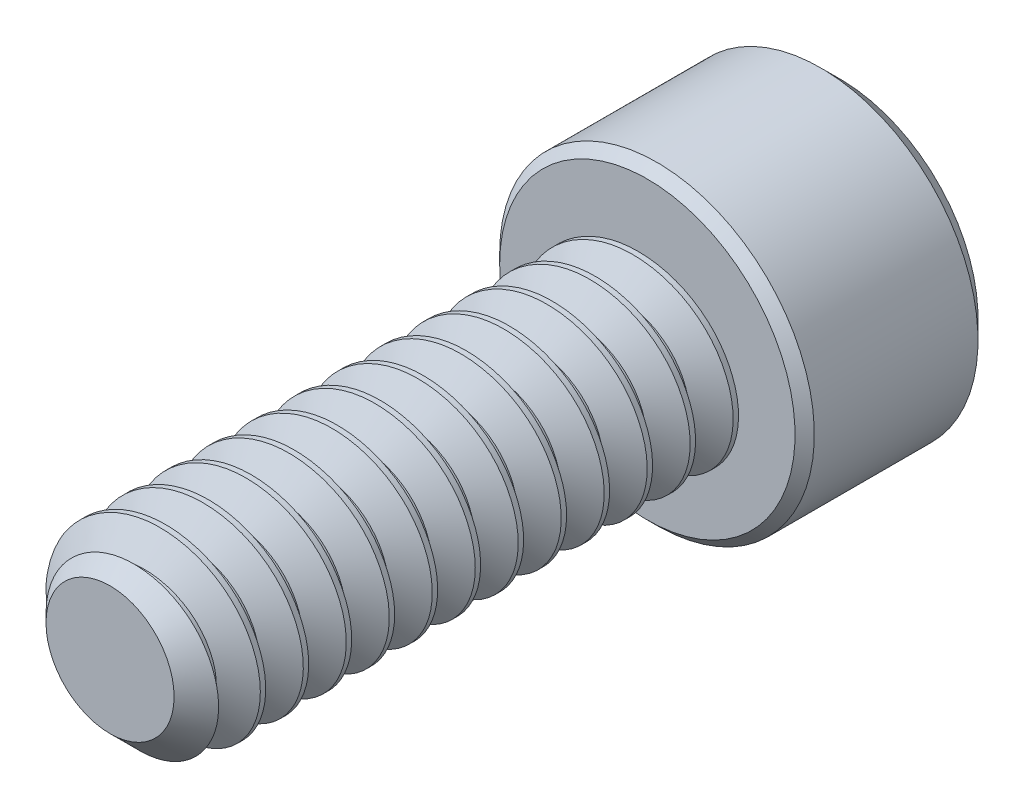
SolidWorks part; units mm, degrees
material "Plain Carbon Steel"
ref_plane "Front Plane" through (0, 0, 0) normal (0, 0, 1) x (1, 0, 0)
ref_plane "Top Plane" through (0, 0, 0) normal (0, 1, 0) x (1, 0, 0)
ref_plane "Right Plane" through (0, 0, 0) normal (1, 0, 0) x (0, 0, -1)
sketch "Sketch1" plane through (0, 0, 0) normal (0, 0, 1) x (1, 0, 0)
  line L0 (0, 1.4224) -> (0, -1.4224) construction
  circle A0 centre (0, 0) radius 1.4224
  dimension "OD" = 2.8448
extrude "Extrude1" add sketch "Sketch1" against normal blind 7.9375
sketch "Sketch2" plane through (0, 0, 0) normal (0, 0, 1) x (1, 0, 0)
  circle A0 centre (0, 0) radius 1.4224 construction
  circle A1 centre (0, 0) radius 1.4224
curve "Helix/Spiral1" pitch 0.635 height 8.5725 radius 1.4224 centre (0, 0, 0) axis (0, 0, -1) start towards (0, 1, 0) parameters "pitch"=0.635
chamfer "Chamfer3" distance 0.4763 angle 45 1 edges at (1.4224, 0, 0)
sketch "Sketch3" plane through (0, 0, 0) normal (1, 0, 0) x (0, 0, -1)
  line L0 (-0.5556, 1.4224) -> (-0.3175, 1.01)
  line L1 (-0.3175, 1.01) -> (-0.2381, 1.01)
  line L2 (-0.2381, 1.01) -> (0, 1.4224)
  line L3 (-0.5556, 1.4224) -> (0, 1.4224)
  line L4 (-0.2778, 1.4224) -> (-0.2778, 1.01) construction
  line L5 (-0.4366, 1.2162) -> (-0.1191, 1.2162) construction
  line L6 (0, 1.4224) -> (0, -1.4224) construction
  dimension "D1" = 0.0794
  dimension "D2" = 0.3175
  dimension "D3" = 60
sweep "Cut-Sweep1" cut profiles "Sketch3" path "Helix/Spiral1" align with end faces yes
sketch "Sketch6" plane through (0, 0, -7.9375) normal (0, 0, -1) x (-1, 0, 0)
  circle A0 centre (0, 0) radius 2.3241
  dimension "head dia" = 4.6482
extrude "Extrude2" add sketch "Sketch6" along normal blind 2.8448
sketch "Sketch7" plane through (0, 0, -10.7823) normal (0, 0, -1) x (-1, 0, 0)
  line L1 (0, 1.3748) -> (-1.1906, 0.6874)
  line L2 (-1.1906, 0.6874) -> (-1.1906, -0.6874)
  line L3 (-1.1906, -0.6874) -> (0, -1.3748)
  line L4 (0, -1.3748) -> (1.1906, -0.6874)
  line L5 (1.1906, -0.6874) -> (1.1906, 0.6874)
  line L6 (1.1906, 0.6874) -> (0, 1.3748)
  circle A0 centre (0, 0) radius 1.1906 construction
  dimension "hex dia" = 2.3813
extrude "Cut-Extrude1" cut sketch "Sketch7" against normal blind 1.7859
sketch "Sketch8" plane through (0, 0, -10.7823) normal (0, 0, -1) x (-1, 0, 0)
  circle A0 centre (0, 0) radius 1.3748
extrude "Cut-Extrude2" cut sketch "Sketch8" against normal blind 0.2845 draft 45
chamfer "Chamfer1" distance 0.2845 angle 45 1 edges at (-2.3241, 0, -10.7823)
chamfer "Chamfer2" distance 0.1422 angle 45 1 edges at (-2.3241, 0, -7.9375)
sketch "Sketch9" plane through (0, 0, 0) normal (1, 0, 0) x (0, 0, -1)
  line L0 (0, 1.4224) -> (0, -1.4224) construction
  line L1 (3.4925, 1.4224) -> (3.4925, -1.4224) construction
  line L2 (7.9375, 2.3241) -> (7.9375, -2.3241) construction
  line L3 (10.7823, 2.3241) -> (10.7823, -2.3241) construction
  line L4 (10.7823, 0) -> (0, 0) construction
  dimension "D1" = 3.4925
  dimension "D2" = 2.8448
  dimension "D3" = 4.6482
  dimension "D4" = 7.9375
equation "\"D3@Helix/Spiral1\" = \"screw length@Extrude1\"+\"pitch@Helix/Spiral1\""
equation "\"D1@Sketch3\" = \"pitch@Helix/Spiral1\"*.125"
equation "\"D2@Sketch3\" = \"pitch@Helix/Spiral1\"*.5"
equation "\"D1@Cut-Extrude1\" = \"hex dia@Sketch7\"*.75"
equation "\"D1@Chamfer1\" = \"head depth@Extrude2\"/10"
equation "\"D1@Sketch9\" = \"pitch@Helix/Spiral1\"*5.5"
equation "\"D1@Chamfer2\" = \"D1@Chamfer1\"/2"
equation "\"D1@Cut-Extrude2\" = \"D1@Chamfer2\"*2"
equation "\"D1@Chamfer3\" = \"pitch@Helix/Spiral1\"*.750"
equation "\"D2@Sketch9\" = \"head depth@Extrude2\""
equation "\"D3@Sketch9\" = \"head dia@Sketch6\""
equation "\"D4@Sketch9\" = \"screw length@Extrude1\""
